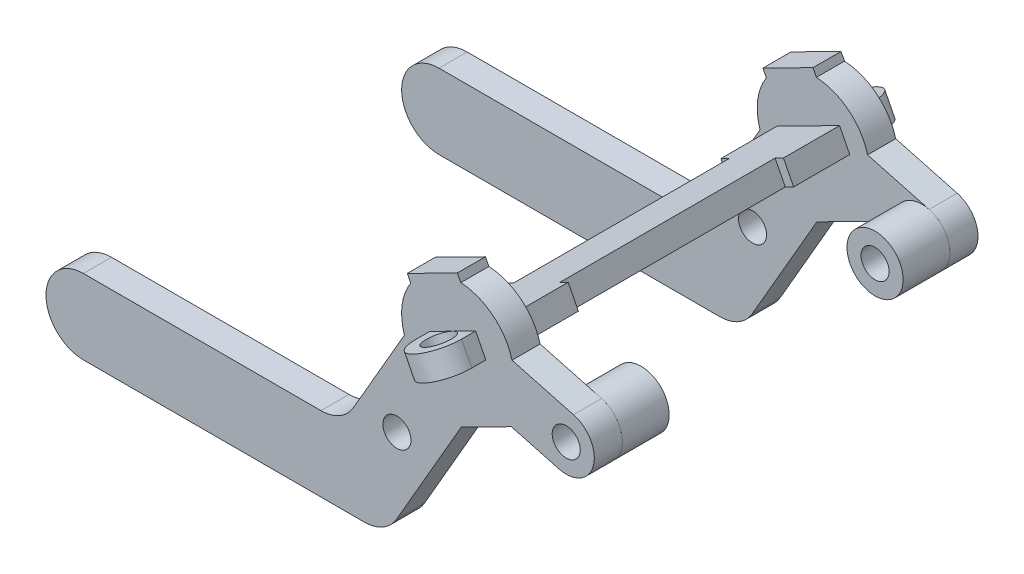
SolidWorks part; units mm, degrees
material "ﾎﾟﾘｵｷｼﾒﾁﾚﾝ(POM)ｱｾﾀｰﾙ共重合体"
ref_plane "正面" through (0, 0, 0) normal (0, 0, 1) x (1, 0, 0)
ref_plane "平面" through (0, 0, 0) normal (0, 1, 0) x (1, 0, 0)
ref_plane "右側面" through (0, 0, 0) normal (1, 0, 0) x (0, 0, -1)
sketch "ｽｹｯﾁ1" plane through (0, 0, 0) normal (0, 0, 1) x (1, 0, 0)
  line L0 (0, 0) -> (-10, -17.3205) construction
  line L1 (-1.5877, -2.75) -> (1.5877, -2.75) construction
  line L2 (1.5877, -2.75) -> (3.1754, 0) construction
  line L3 (3.1754, 0) -> (1.5877, 2.75) construction
  line L4 (1.5877, 2.75) -> (-1.5877, 2.75) construction
  line L5 (-1.5877, 2.75) -> (-3.1754, 0) construction
  line L6 (-3.1754, 0) -> (-1.5877, -2.75) construction
  line L7 (-10, -17.3205) -> (-40, -17.3205) construction
  line L8 (-5.7002, -1.873) -> (-11.1547, -11.3205)
  line L9 (-14.6188, -13.3205) -> (-40, -13.3205)
  line L10 (0.3718, -7.3561) -> (-6.5359, -19.3205)
  line L11 (-10, -21.3205) -> (-40, -21.3205)
  line L12 (-3.4641, 2) -> (-12.3094, -13.3205) construction
  line L13 (-12.3094, -13.3205) -> (-40, -13.3205) construction
  line L14 (3.4641, -2) -> (-7.6906, -21.3205) construction
  line L15 (-7.6906, -21.3205) -> (-40, -21.3205) construction
  line L16 (5.7956, 1.5529) -> (12.3676, -0.2081)
  line L18 (10.8147, -6.0036) -> (5.7212, -4.6388)
  line L23 (11.5911, -3.1058) -> (0, 0) construction
  line L24 (-0.0426, 6.7081) -> (0.3215, 5.9914)
  line L25 (-1.9088, -2.3144) -> (-2.9948, -0.1765)
  line L26 (-1.9088, -2.3144) -> (2.9948, 0.1765)
  line L27 (2.9948, 0.1765) -> (1.9088, 2.3144)
  line L28 (-2.9948, -0.1765) -> (1.9088, 2.3144)
  line L29 (-1.9088, -2.3144) -> (1.9088, 2.3144) construction
  line L30 (2.9948, 0.1765) -> (-2.9948, -0.1765) construction
  line L31 (-0.0426, 6.7081) -> (-5.392, 3.9908)
  line L32 (5.7212, -4.6388) -> (0.3718, -7.3561)
  line L33 (-5.392, 3.9908) -> (-5.028, 3.2741)
  line L34 (-0.0426, 6.7081) -> (0.3718, -7.3561) construction
  line L35 (5.7212, -4.6388) -> (-5.392, 3.9908) construction
  line L36 (3.0465, -5.9975) -> (-2.7173, 5.3494) construction
  line L37 (5.7212, -4.6388) -> (4.2426, -4.2426) construction
  line L38 (1.228, -5.873) -> (0.3718, -7.3561) construction
  line L39 (-0.3215, -5.9914) -> (0.3718, -7.3561) construction
  line L40 (-1.79, -3.1004) -> (-0.3215, -5.9914) construction
  line L41 (-5.028, 3.2741) -> (-1.79, -3.1004) construction
  line L42 (5.028, -3.2741) -> (5.7212, -4.6388) construction
  line L43 (3.895, -1.0437) -> (5.028, -3.2741) construction
  line L44 (0.3215, 5.9914) -> (3.895, -1.0437) construction
  circle A0 centre (0, 0) radius 2.75 construction
  arc A2 (-40, -13.3205) -> (-40, -21.3205) centre (-40, -17.3205) ccw
  arc A3 (-11.1547, -11.3205) -> (-14.6188, -13.3205) centre (-14.6188, -9.3205) cw
  arc A4 (-6.5359, -19.3205) -> (-10, -21.3205) centre (-10, -17.3205) cw
  arc A5 (5.7956, 1.5529) -> (0.3215, 5.9914) centre (0, 0) ccw
  arc A6 (12.3676, -0.2081) -> (10.8147, -6.0036) centre (11.5911, -3.1058) cw
  arc A7 (4.2426, -4.2426) -> (5.7956, 1.5529) centre (0, 0) ccw construction
  arc A8 (1.228, -5.873) -> (2.7173, -5.3494) centre (0, 0) ccw construction
  arc A9 (-3, -5.1962) -> (1.228, -5.873) centre (0, 0) ccw construction
  arc A10 (-5.7002, -1.873) -> (-3, -5.1962) centre (0, 0) ccw construction
  circle A11 centre (11.5911, -3.1058) radius 1.5
  circle A12 centre (-6.5, -11.2583) radius 1.5
  arc A13 (-5.028, 3.2741) -> (-5.7002, -1.873) centre (0, 0) ccw
  arc A14 (-0.0217, 6) -> (-2.7173, 5.3494) centre (0, 0) ccw construction
  arc A15 (0.3215, 5.9914) -> (-0.0217, 6) centre (0, 0) ccw construction
  arc A16 (-2.7173, 5.3494) -> (-4.8325, 3.5563) centre (0, 0) ccw construction
  arc A17 (-4.8325, 3.5563) -> (-5.028, 3.2741) centre (0, 0) ccw construction
  arc A18 (2.7173, -5.3494) -> (4.2426, -4.2426) centre (0, 0) ccw construction
  point P38 (0, 0)
  point P39 (0.1646, -0.324)
  dimension "D1" = 5.5
  dimension "D6" = 12
  dimension "D7" = 12
  dimension "D8" = 3
  dimension "D10" = 3
  dimension "D11" = 3
  dimension "D2" = 120
  dimension "D3" = 20
  dimension "D4" = 30
  dimension "D5" = 4
  dimension "D9" = 75
  dimension "D12" = 13
  dimension "D13" = 6
  dimension "D14" = 5.5
  dimension "D15" = 6
extrude "ﾎﾞｽ - 押し出し1" add sketch "ｽｹｯﾁ1" along normal mid plane 3
pattern_linear "直線ﾊﾟﾀｰﾝ1" count 2 spacing 38 along (0, 0, 1) of bodies 101
ref_plane "平面1" through (0, 0, 19) normal (0, 0, -1) x (-1, 0, 0)
sketch "ｽｹｯﾁ2" plane through (0, 0, 39.5) normal (0, 0, 1) x (1, 0, 0)
  line L5 (-2.9948, -0.1765) -> (-1.9088, -2.3144)
  line L6 (1.9088, 2.3144) -> (-2.9948, -0.1765)
  line L19 (2.9948, 0.1765) -> (1.9088, 2.3144)
  line L20 (-1.9088, -2.3144) -> (2.9948, 0.1765)
  line L21 (-2.9948, -0.1765) -> (-1.9088, -2.3144)
  line L22 (1.9088, 2.3144) -> (-2.9948, -0.1765)
  line L23 (2.9948, 0.1765) -> (1.9088, 2.3144)
  line L24 (-1.9088, -2.3144) -> (2.9948, 0.1765)
  circle A0 centre (0, 0) radius 1.6 construction
  dimension "D2" = 3.2
  dimension "D1" = 0
extrude "ﾎﾞｽ - 押し出し2" add sketch "ｽｹｯﾁ2" against normal up to surface (41 mm away) separate body up to face at (-5, -11.2583, -1.5)
sketch "ｽｹｯﾁ4" plane through (0, 0, 1.5) normal (0, 0, 1) x (1, 0, 0)
  circle A0 centre (11.5911, -3.1058) radius 3
  circle A1 centre (11.5911, -3.1058) radius 1.5 construction
  circle A2 centre (11.5911, -3.1058) radius 1.5
  dimension "D1" = 6
extrude "ﾎﾞｽ - 押し出し3" add sketch "ｽｹｯﾁ4" along normal blind 5 separate body
mirror "ﾐﾗｰ1" about plane through (0, 0, 19) normal (0, 0, -1) of bodies 104
sketch "ｽｹｯﾁ5" plane through (-0.543, 1.069, 0) normal (-0.4529, 0.8916, 0) x (0, 0, 1)
  line L0 (0, 0) -> (4.5, 0) construction
  line L1 (1.5, 3.75) -> (7.5, 3.75)
  line L2 (1.5, 3.75) -> (1.5, -3.75)
  line L3 (1.5, -3.75) -> (7.5, -3.75)
  line L4 (7.5, 3.75) -> (7.5, -3.75)
  line L5 (1.5, 3.75) -> (7.5, -3.75) construction
  line L6 (1.5, -3.75) -> (7.5, 3.75) construction
  line L7 (-1.5, -2.75) -> (39.5, -2.75) construction
  line L8 (19, 55) -> (19, -55) construction
  line L9 (36.5, -3.75) -> (30.5, -3.75)
  line L10 (30.5, 3.75) -> (30.5, -3.75)
  line L11 (36.5, 3.75) -> (30.5, 3.75)
  line L12 (36.5, 3.75) -> (36.5, -3.75)
  line L13 (1.5, 2.75) -> (1.5, -2.75) construction
  line L14 (-1.5, 11.9277) -> (-1.5, 6.9231) construction
  line L15 (-3, -2.75) -> (-0.5, -2.75)
  line L16 (-3, -2.75) -> (-3, 2.75) construction
  line L17 (-3, 2.75) -> (-0.5, 2.75)
  line L18 (-0.5, -2.75) -> (-0.5, 2.75)
  line L19 (-3, -2.75) -> (-0.5, 2.75) construction
  line L20 (-3, 2.75) -> (-0.5, -2.75) construction
  line L21 (0, 0) -> (-1.75, 0) construction
  line L22 (41, -2.75) -> (38.5, -2.75)
  line L23 (38.5, -2.75) -> (38.5, 2.75)
  line L24 (41, 2.75) -> (38.5, 2.75)
  circle A0 centre (-3, 0) radius 1.5
  arc A1 (-3, -2.75) -> (-3, 2.75) centre (-3, 0) cw
  arc A2 (41, -2.75) -> (41, 2.75) centre (41, 0) ccw
  circle A3 centre (41, 0) radius 1.5
  point P0 (4.5, 0)
  point P19 (0, 0)
  point P22 (-1.75, 0)
  point P29 (-3.5813, -2.7391)
  point P30 (0, 0)
  point P38 (-0.6342, -3)
  dimension "D2" = 3
  dimension "D1" = 23
  dimension "D3" = 1
  dimension "D5" = 1
extrude "ﾎﾞｽ - 押し出し5" add sketch "ｽｹｯﾁ5" against normal up to surface (2.3979 mm away) up to face at (0.543, -1.069, 19)
